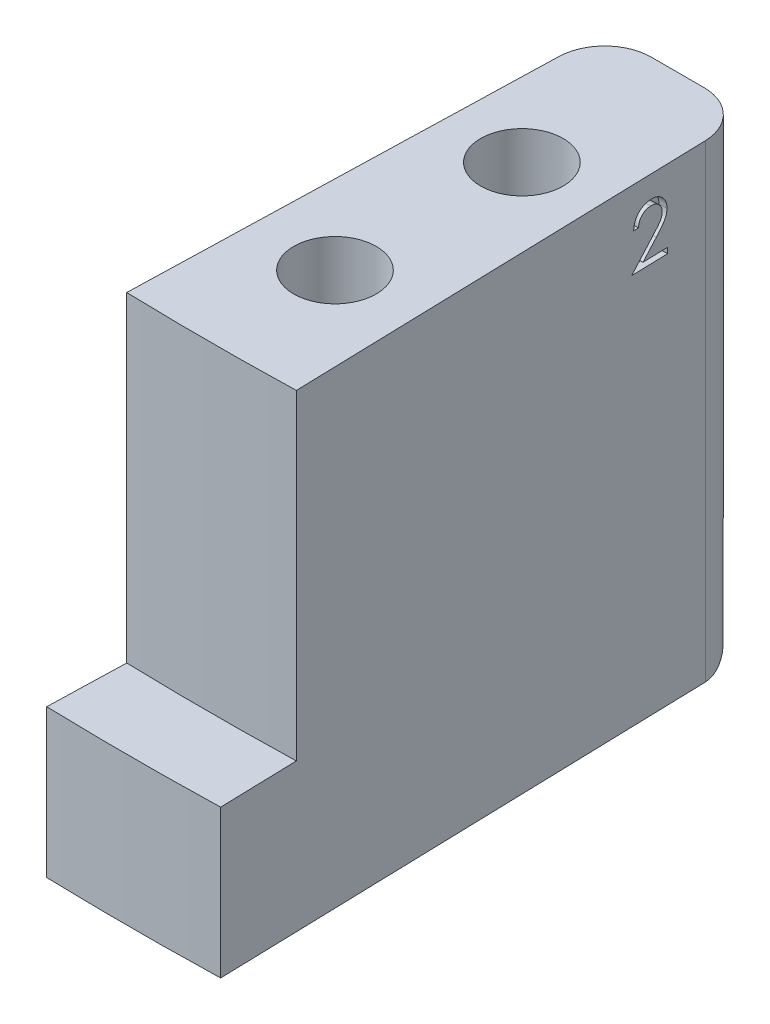
SolidWorks part; units mm, degrees
ref_plane "前视基准面" through (0, 0, 0) normal (0, 0, 1) x (1, 0, 0)
ref_plane "上视基准面" through (0, 0, 0) normal (0, 1, 0) x (1, 0, 0)
ref_plane "右视基准面" through (0, 0, 0) normal (1, 0, 0) x (0, 0, -1)
ref_axis "顶盖中心轴" through (0, -55, 0) along (0, 1, 0)
sketch "草图1" plane through (0, 0, 0) normal (0, 1, 0) x (1, 0, 0)
  line L0 (-4.7487, -170.0072) -> (-4.8586, -173.9402) construction
  line L1 (0, 0) -> (0, -125.794) construction
  line L3 (-4.6089, -165) -> (4.6089, -165)
  line L4 (-4.6089, -165) -> (-5.5843, -199.922)
  line L5 (4.6089, -165) -> (5.5843, -199.922)
  arc A0 (-5.4447, -194.924) -> (5.4447, -194.924) centre (0, 0) ccw
  arc A1 (-5.5843, -199.922) -> (5.5843, -199.922) centre (0, 0) ccw
  dimension "D1" = 1.6
  dimension "D2" = 195
  dimension "D4" = 200
  dimension "D3" = 165
extrude "主体" add sketch "草图1" along normal blind 30.1 contours L4 A0 L5 L3 region at (0, 0, 180.4033)
extrude "插销" add sketch "草图1<3>" along normal blind 9.5 contours L4 A1 L5 A0 region at (0, 0, 197.4849)
sketch "草图1<3>" plane through (0, 0, 0) normal (0, 1, 0) x (1, 0, 0) same geometry as "草图1"
ref_plane "对称面" through (0, 0, 0) normal (1, 0, 0) x (0, 0, -1)
fillet "圆角1" radius 3 3 edges at (-4.6089, 15.05, 165) (4.6089, 15.05, 165) (0, 0, 165)
hole_wizard "M5 间隙孔1" positions "草图4" profile "草图5" hole size "M5" standard "ISO" end condition up to next
sketch "草图4" plane through (0, 30.1, 0) normal (0, 1, 0) x (1, 0, 0)
  line L0 (0, -13.75) -> (0, 13.75) construction
  point P0 (0, -187)
  point P2 (0, -175)
  dimension "D1" = 175
  dimension "D2" = 187
sketch "草图5" plane through (0, 30.1, 187) normal (1, 0, 0) x (0, 0, 1)
  line L0 (0, 0) -> (0, 30.1)
  line L1 (0, 30.1) -> (2.65, 30.1)
  line L2 (2.65, 30.1) -> (2.65, 0)
  line L5 (2.65, 0) -> (0, 0)
  line L11 (0, -6.35) -> (0, 107.95) construction
  dimension "通孔孔直径" = 5.3
  dimension "通孔孔深度" = 30.1
sketch "草图6" plane through (0, 0, 0) normal (0, -1, 0) x (1, 0, 0)
  line L1 (0, 179.6188) -> (-4, 177.3094)
  line L2 (-4, 177.3094) -> (-4, 172.6906)
  line L3 (-4, 172.6906) -> (0, 170.3812)
  line L4 (0, 170.3812) -> (4, 172.6906)
  line L5 (4, 172.6906) -> (4, 177.3094)
  line L6 (4, 177.3094) -> (0, 179.6188)
  line L7 (0, 191.6188) -> (-4, 189.3094)
  line L8 (-4, 189.3094) -> (-4, 184.6906)
  line L9 (-4, 184.6906) -> (0, 182.3812)
  line L10 (0, 182.3812) -> (4, 184.6906)
  line L11 (4, 184.6906) -> (4, 189.3094)
  line L12 (4, 189.3094) -> (0, 191.6188)
  circle A0 centre (0, 175) radius 4 construction
  circle A1 centre (0, 187) radius 4 construction
  dimension "D1" = 8
  dimension "D2" = 8
extrude "切除-拉伸1" cut sketch "草图6" against normal blind 5
sketch "草图7" plane through (0, 0, 0) normal (0.9996, 0, -0.0279) x (-0.0279, 0, -0.9996)
  line L0 (-167.9817, 0.0012) -> (-167.9817, 30.1) construction
  line L2 (-167.9817, 30.1) -> (-195, 30.1) construction
  text T0 "2"
  dimension "D1" = 5
  dimension "D2" = 5
extrude "切除-拉伸2" cut sketch "草图7" against normal blind 0.5
